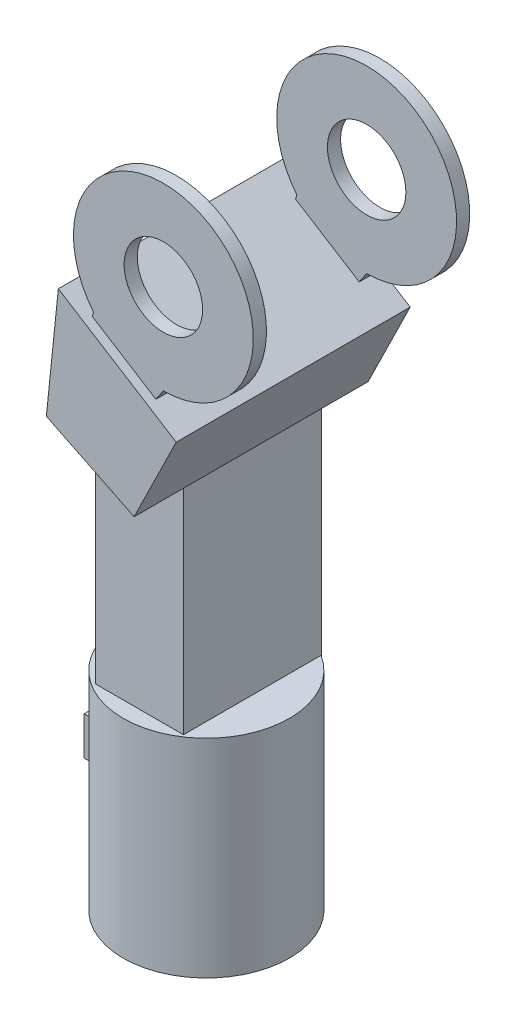
SolidWorks part; units mm, degrees
ref_plane "Front Plane" through (0, 0, 0) normal (0, 0, 1) x (1, 0, 0)
ref_plane "Top Plane" through (0, 0, 0) normal (0, 1, 0) x (1, 0, 0)
ref_plane "Right Plane" through (0, 0, 0) normal (1, 0, 0) x (0, 0, -1)
sketch "Sketch1" plane through (0, 0, 0) normal (0, 1, 0) x (1, 0, 0)
  circle A0 centre (-0.0222, -0.0002) radius 0.0284
extrude "Boss-Extrude1" add sketch "Sketch1" against normal blind 0.071 from offset 0.143 offset against normal yes
sketch "Sketch2" plane through (0, 0, 0) normal (1, 0, 0) x (0, 0, -1)
  line L1 (0.0077, -0.1688) -> (-0.0081, -0.1688)
  line L2 (0.0077, -0.1688) -> (0.0077, -0.1819)
  line L3 (0.0077, -0.1819) -> (-0.0081, -0.1819)
  line L4 (-0.0081, -0.1688) -> (-0.0081, -0.1819)
extrude "Boss-Extrude2" add sketch "Sketch2" against normal blind 0.056
sketch "Sketch3" plane through (0, 0, 0) normal (1, 0, 0) x (0, 0, -1)
  line L1 (0.024, -0.0502) -> (-0.0231, -0.0502)
  line L2 (0.024, -0.0502) -> (0.024, -0.1457)
  line L3 (0.024, -0.1457) -> (-0.0231, -0.1457)
  line L4 (-0.0231, -0.0502) -> (-0.0231, -0.1457)
extrude "Boss-Extrude3" add sketch "Sketch3" against normal blind 0.03 from offset 0.007 offset against normal yes
sketch "Sketch4" plane through (0, 0, 0) normal (0, 0, 1) x (1, 0, 0)
  line L0 (0.0074, -0.0407) -> (-0.007, -0.07)
  line L2 (-0.007, -0.07) -> (-0.037, -0.0553)
  line L4 (-0.037, -0.0553) -> (-0.0329, -0.0155)
  line L5 (-0.0329, -0.0155) -> (0.0074, -0.0407)
  point P2 (0, 0)
  point P3 (0, 0)
  point P5 (0, 0)
  point P6 (0, 0)
  point P9 (0, 0)
  point P10 (0, 0)
  point P11 (0, 0)
  point P12 (0, 0)
extrude "Boss-Extrude4" add sketch "Sketch4" along normal blind 0.04 and the other way blind 0.04
sketch "Sketch6" plane through (0, 0, 0) normal (0, 0, 1) x (1, 0, 0)
  line L0 (-0.0243, -0.0209) -> (-0.0239, -0.0194)
  line L1 (0.0074, -0.0407) -> (-0.0329, -0.0155) construction
  line L2 (-0.0243, -0.0209) -> (-0.0025, -0.0345)
  line L3 (-0.0025, -0.0345) -> (0, -0.0307)
  arc A0 (0, -0.0307) -> (-0.0239, -0.0194) centre (0, 0) ccw
  circle A1 centre (0, 0) radius 0.0134
extrude "Boss-Extrude5" add sketch "Sketch6" along normal blind 0.0045 from offset 0.0325
extrude "Boss-Extrude6" add sketch "Sketch6<3>" against normal blind 0.0045 from offset 0.0325 offset against normal yes
sketch "Sketch6<3>" plane through (0, 0, 0) normal (0, 0, 1) x (1, 0, 0) same geometry as "Sketch6"
